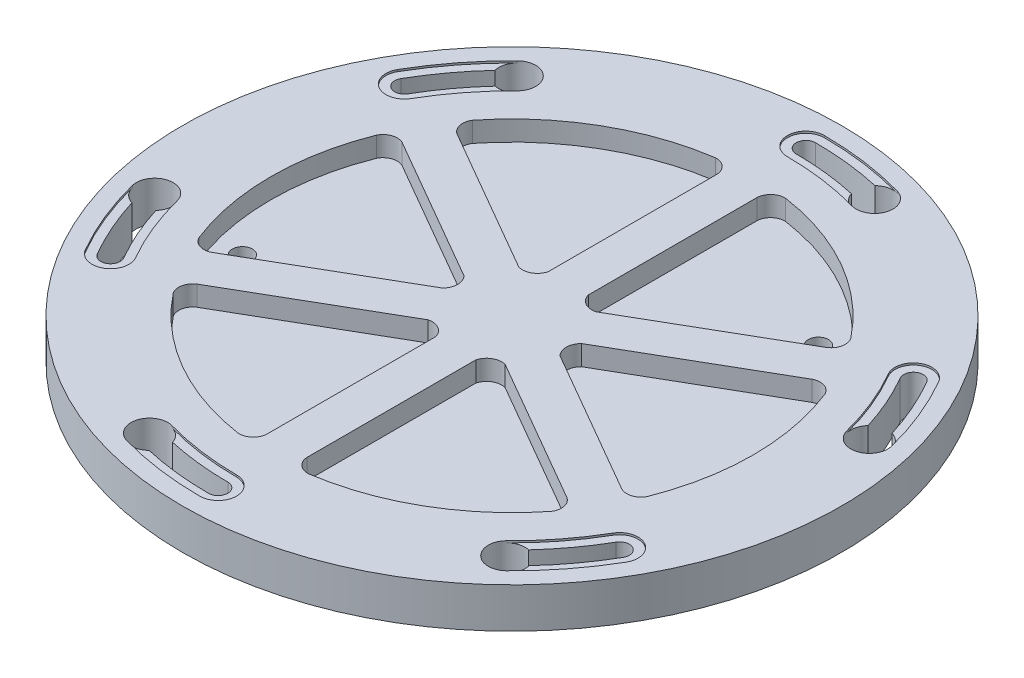
SolidWorks part; units mm, degrees
material "1060 Alloy"
ref_plane "Front Plane" through (0, 0, 0) normal (0, 0, 1) x (1, 0, 0)
ref_plane "Top Plane" through (0, 0, 0) normal (0, 1, 0) x (1, 0, 0)
ref_plane "Right Plane" through (0, 0, 0) normal (1, 0, 0) x (0, 0, -1)
sketch "Sketch1" plane through (0, 0, 0) normal (0, 1, 0) x (1, 0, 0)
  circle A0 centre (0, 0) radius 82
  arc A1 (0, 77.7102) -> (0, 68.5398) centre (0, 73.125) ccw
  arc A2 (0, 73.125) -> (19.8133, 70.3896) centre (0, 0) cw construction
  arc A3 (20.4672, 72.7124) -> (0, 75.5381) centre (0, 0) ccw construction
  arc A4 (19.1595, 68.0668) -> (0, 70.7119) centre (0, 0) ccw construction
  arc A5 (19.1595, 68.0668) -> (20.4672, 72.7124) centre (19.8133, 70.3896) ccw construction
  arc A6 (0, 75.5381) -> (0, 70.7119) centre (0, 73.125) ccw construction
  arc A7 (0, 73.125) -> (19.8133, 70.3896) centre (0, 0) cw construction
  arc A8 (21.0557, 74.8033) -> (0, 77.7102) centre (0, 0) ccw construction
  arc A9 (18.571, 65.9759) -> (0, 68.5398) centre (0, 0) ccw construction
  arc A10 (18.571, 65.9759) -> (21.0557, 74.8033) centre (19.8133, 70.3896) ccw construction
  arc A11 (0, 77.7102) -> (0, 68.5398) centre (0, 73.125) ccw construction
  arc A12 (15.4421, 69.0052) -> (16.6259, 73.6857) centre (19.8133, 70.3896) ccw
  arc A13 (0, 75.5381) -> (0, 70.7119) centre (0, 73.125) ccw
  arc A14 (0, 70.7119) -> (15.4421, 69.0052) centre (0, 0) cw
  arc A15 (0, 75.5381) -> (16.6259, 73.6857) centre (0, 0) cw
  arc A16 (0, 77.7102) -> (21.0557, 74.8033) centre (0, 0) cw
  arc A17 (0, 68.5398) -> (18.571, 65.9759) centre (0, 0) cw
  circle A18 centre (0, 0) radius 82
  arc A19 (67.299, 38.8551) -> (59.3572, 34.2699) centre (63.3281, 36.5625) ccw
  arc A20 (65.4179, 37.769) -> (61.2383, 35.356) centre (63.3281, 36.5625) ccw
  arc A21 (65.4179, 37.769) -> (72.1266, 22.4444) centre (0, 0) cw
  arc A22 (67.299, 38.8551) -> (75.3094, 19.1669) centre (0, 0) cw
  arc A23 (67.4813, 21.1293) -> (72.1266, 22.4444) centre (70.8659, 18.036) ccw
  arc A24 (61.2383, 35.356) -> (67.4813, 21.1293) centre (0, 0) cw
  arc A25 (59.3572, 34.2699) -> (66.4223, 16.905) centre (0, 0) cw
  circle A26 centre (0, 0) radius 82
  arc A27 (67.299, -38.8551) -> (59.3572, -34.2699) centre (63.3281, -36.5625) ccw
  arc A28 (65.4179, -37.769) -> (61.2383, -35.356) centre (63.3281, -36.5625) ccw
  arc A29 (65.4179, -37.769) -> (55.5007, -51.2413) centre (0, 0) cw
  arc A30 (67.299, -38.8551) -> (54.2537, -55.6364) centre (0, 0) cw
  arc A31 (52.0392, -47.8759) -> (55.5007, -51.2413) centre (51.0525, -52.3537) ccw
  arc A32 (61.2383, -35.356) -> (52.0392, -47.8759) centre (0, 0) cw
  arc A33 (59.3572, -34.2699) -> (47.8513, -49.0709) centre (0, 0) cw
  circle A34 centre (0, 0) radius 82
  arc A35 (0, -77.7102) -> (0, -68.5398) centre (0, -73.125) ccw
  arc A36 (0, -75.5381) -> (0, -70.7119) centre (0, -73.125) ccw
  arc A37 (0, -75.5381) -> (-16.6259, -73.6857) centre (0, 0) cw
  arc A38 (0, -77.7102) -> (-21.0557, -74.8033) centre (0, 0) cw
  arc A39 (-15.4421, -69.0052) -> (-16.6259, -73.6857) centre (-19.8133, -70.3896) ccw
  arc A40 (0, -70.7119) -> (-15.4421, -69.0052) centre (0, 0) cw
  arc A41 (0, -68.5398) -> (-18.571, -65.9759) centre (0, 0) cw
  circle A42 centre (0, 0) radius 82
  arc A43 (-67.299, -38.8551) -> (-59.3572, -34.2699) centre (-63.3281, -36.5625) ccw
  arc A44 (-65.4179, -37.769) -> (-61.2383, -35.356) centre (-63.3281, -36.5625) ccw
  arc A45 (-65.4179, -37.769) -> (-72.1266, -22.4444) centre (0, 0) cw
  arc A46 (-67.299, -38.8551) -> (-75.3094, -19.1669) centre (0, 0) cw
  arc A47 (-67.4813, -21.1293) -> (-72.1266, -22.4444) centre (-70.8659, -18.036) ccw
  arc A48 (-61.2383, -35.356) -> (-67.4813, -21.1293) centre (0, 0) cw
  arc A49 (-59.3572, -34.2699) -> (-66.4223, -16.905) centre (0, 0) cw
  circle A50 centre (0, 0) radius 82
  arc A51 (-67.299, 38.8551) -> (-59.3572, 34.2699) centre (-63.3281, 36.5625) ccw
  arc A52 (-65.4179, 37.769) -> (-61.2383, 35.356) centre (-63.3281, 36.5625) ccw
  arc A53 (-65.4179, 37.769) -> (-55.5007, 51.2413) centre (0, 0) cw
  arc A54 (-67.299, 38.8551) -> (-54.2537, 55.6364) centre (0, 0) cw
  arc A55 (-52.0392, 47.8759) -> (-55.5007, 51.2413) centre (-51.0525, 52.3537) ccw
  arc A56 (-61.2383, 35.356) -> (-52.0392, 47.8759) centre (0, 0) cw
  arc A57 (-59.3572, 34.2699) -> (-47.8513, 49.0709) centre (0, 0) cw
  point P7 (10.0006, 72.4379)
  point P15 (10.0006, 72.4379)
  point P111 (0, 0)
  dimension "D1" = 6
extrude "Boss-Extrude1" add sketch "Sketch1" along normal blind 10 contours A0 A57 A51 A54 A55 A49 A43 A46 A47 A41 A35 A38 A39 A33 A27 A30 A31 A25 A19 A22 A23 A17 A1 A16 A12 region at (0, 0, 0)
extrude "Boss-Extrude3" add sketch "Sketch1<4>" along normal blind 9.525 contours A43 A49 A47 A48 A44 A45 A46 region at (-71.7086, 0, 29.1755)
sketch "Sketch1<4>" plane through (0, 0, 0) normal (0, 1, 0) x (1, 0, 0) same geometry as "Sketch1"
pattern_circular "CirPattern1" count 6 over 360 about axis through (0, 10, 0) along (0, 1, 0) of "Boss-Extrude3"
sketch "Sketch2" plane through (0, 10, 0) normal (0, 1, 0) x (1, 0, 0)
  line L0 (-28.4808, 10.6699) -> (-51.0159, 23.6805)
  line L1 (-28.4808, 10.6699) -> (-14.6202, 2.6675)
  line L2 (-14.6202, -2.6675) -> (-28.4808, -10.6699)
  line L3 (-28.4808, -10.6699) -> (-51.0159, -23.6805)
  line L4 (-5, 30) -> (-5, 56.0213)
  line L5 (-5, 30) -> (-5, 13.9952)
  line L6 (-9.6202, 11.3277) -> (-23.4808, 19.3301)
  line L7 (-23.4808, 19.3301) -> (-46.0159, 32.3408)
  line L8 (-23.4808, -19.3301) -> (-9.6202, -11.3277)
  line L9 (-5, -13.9952) -> (-5, -30)
  line L10 (-23.4808, -19.3301) -> (-46.0159, -32.3408)
  line L11 (-5, -30) -> (-5, -56.0213)
  line L12 (23.4808, 19.3301) -> (46.0159, 32.3408)
  line L13 (23.4808, 19.3301) -> (9.6202, 11.3277)
  line L14 (5, 13.9952) -> (5, 30)
  line L15 (5, 30) -> (5, 56.0213)
  line L16 (28.4808, -10.6699) -> (51.0159, -23.6805)
  line L17 (28.4808, -10.6699) -> (14.6202, -2.6675)
  line L18 (14.6202, 2.6675) -> (28.4808, 10.6699)
  line L19 (28.4808, 10.6699) -> (51.0159, 23.6805)
  line L20 (5, -30) -> (5, -56.0213)
  line L21 (5, -30) -> (5, -13.9952)
  line L22 (9.6202, -11.3277) -> (23.4808, -19.3301)
  line L23 (23.4808, -19.3301) -> (46.0159, -32.3408)
  arc A0 (-47.034, -37.2532) -> (-8.7452, -59.3593) centre (0, 0) ccw
  arc A1 (-9.6202, -11.3277) -> (-5, -13.9952) centre (-8.6438, -14.9716) cw
  arc A2 (-47.034, -37.2532) -> (-8.7452, -59.3593) centre (0, 0) ccw
  arc A3 (-47.034, -37.2532) -> (-46.0159, -32.3408) centre (-44.0688, -35.3061) cw
  arc A4 (-5, -56.0213) -> (-8.7452, -59.3593) centre (-8.5416, -55.8177) cw
  arc A5 (-55.7792, 22.1061) -> (-51.0159, 23.6805) centre (-52.6103, 20.5116) cw
  arc A6 (-14.6202, 2.6675) -> (-14.6202, -2.6675) centre (-17.2877, 0) cw
  arc A7 (-51.0159, -23.6805) -> (-55.7792, -22.1061) centre (-52.6103, -20.5116) cw
  arc A8 (-47.034, -37.2532) -> (-8.7452, -59.3593) centre (0, 0) ccw
  arc A9 (-8.7452, 59.3593) -> (-5, 56.0213) centre (-8.5416, 55.8177) cw
  arc A10 (-5, 13.9952) -> (-9.6202, 11.3277) centre (-8.6438, 14.9716) cw
  arc A11 (-46.0159, 32.3408) -> (-47.034, 37.2532) centre (-44.0688, 35.3061) cw
  arc A12 (-47.034, -37.2532) -> (-8.7452, -59.3593) centre (0, 0) ccw
  arc A13 (47.034, 37.2532) -> (46.0159, 32.3408) centre (44.0688, 35.3061) cw
  arc A14 (9.6202, 11.3277) -> (5, 13.9952) centre (8.6438, 14.9716) cw
  arc A15 (5, 56.0213) -> (8.7452, 59.3593) centre (8.5416, 55.8177) cw
  arc A16 (-47.034, -37.2532) -> (-8.7452, -59.3593) centre (0, 0) ccw
  arc A17 (55.7792, -22.1061) -> (51.0159, -23.6805) centre (52.6103, -20.5116) cw
  arc A18 (14.6202, -2.6675) -> (14.6202, 2.6675) centre (17.2877, 0) cw
  arc A19 (51.0159, 23.6805) -> (55.7792, 22.1061) centre (52.6103, 20.5116) cw
  arc A20 (-47.034, -37.2532) -> (-8.7452, -59.3593) centre (0, 0) ccw
  arc A21 (8.7452, -59.3593) -> (5, -56.0213) centre (8.5416, -55.8177) cw
  arc A22 (5, -13.9952) -> (9.6202, -11.3277) centre (8.6438, -14.9716) cw
  arc A23 (46.0159, -32.3408) -> (47.034, -37.2532) centre (44.0688, -35.3061) cw
  arc A24 (8.7452, -59.3593) -> (47.034, -37.2532) centre (0, 0) ccw
  arc A25 (8.7452, -59.3593) -> (47.034, -37.2532) centre (0, 0) ccw
  arc A26 (8.7452, -59.3593) -> (47.034, -37.2532) centre (0, 0) ccw
  arc A27 (8.7452, -59.3593) -> (47.034, -37.2532) centre (0, 0) ccw
  arc A28 (8.7452, -59.3593) -> (47.034, -37.2532) centre (0, 0) ccw
  arc A29 (8.7452, -59.3593) -> (47.034, -37.2532) centre (0, 0) ccw
  arc A30 (-55.7792, 22.1061) -> (-55.7792, -22.1061) centre (0, 0) ccw
  arc A31 (-55.7792, 22.1061) -> (-55.7792, -22.1061) centre (0, 0) ccw
  arc A32 (-55.7792, 22.1061) -> (-55.7792, -22.1061) centre (0, 0) ccw
  arc A33 (-55.7792, 22.1061) -> (-55.7792, -22.1061) centre (0, 0) ccw
  arc A34 (-55.7792, 22.1061) -> (-55.7792, -22.1061) centre (0, 0) ccw
  arc A35 (-55.7792, 22.1061) -> (-55.7792, -22.1061) centre (0, 0) ccw
  arc A36 (-8.7452, 59.3593) -> (-47.034, 37.2532) centre (0, 0) ccw
  arc A37 (-8.7452, 59.3593) -> (-47.034, 37.2532) centre (0, 0) ccw
  arc A38 (-8.7452, 59.3593) -> (-47.034, 37.2532) centre (0, 0) ccw
  arc A39 (-8.7452, 59.3593) -> (-47.034, 37.2532) centre (0, 0) ccw
  arc A40 (-8.7452, 59.3593) -> (-47.034, 37.2532) centre (0, 0) ccw
  arc A41 (-8.7452, 59.3593) -> (-47.034, 37.2532) centre (0, 0) ccw
  arc A42 (47.034, 37.2532) -> (8.7452, 59.3593) centre (0, 0) ccw
  arc A43 (47.034, 37.2532) -> (8.7452, 59.3593) centre (0, 0) ccw
  arc A44 (47.034, 37.2532) -> (8.7452, 59.3593) centre (0, 0) ccw
  arc A45 (47.034, 37.2532) -> (8.7452, 59.3593) centre (0, 0) ccw
  arc A46 (47.034, 37.2532) -> (8.7452, 59.3593) centre (0, 0) ccw
  arc A47 (47.034, 37.2532) -> (8.7452, 59.3593) centre (0, 0) ccw
  arc A48 (55.7792, -22.1061) -> (55.7792, 22.1061) centre (0, 0) ccw
  arc A49 (55.7792, -22.1061) -> (55.7792, 22.1061) centre (0, 0) ccw
  arc A50 (55.7792, -22.1061) -> (55.7792, 22.1061) centre (0, 0) ccw
  arc A51 (55.7792, -22.1061) -> (55.7792, 22.1061) centre (0, 0) ccw
  arc A52 (55.7792, -22.1061) -> (55.7792, 22.1061) centre (0, 0) ccw
  arc A53 (55.7792, -22.1061) -> (55.7792, 22.1061) centre (0, 0) ccw
  point P83 (0, 0)
  dimension "D1" = 6
extrude "Cut-Extrude1" cut sketch "Sketch2" against normal blind 5 contours A5 A30 A7 L3 L2 A6 L1 L0 | A9 A36 A11 L7 L6 A10 L5 L4 | A13 A42 A15 L15 L14 A14 L13 L12 | A17 A48 A19 L19 L18 A18 L17 L16 | A21 A24 A23 L23 L22 A22 L21 L20 | A4 L11 L9 A1 L8 L10 A3 A0 region at (-42.1694, 10, 0) region at (-21.0847, 10, -36.5198) region at (-21.0847, 10, 36.5198) region at (21.0847, 10, -36.5198) region at (42.1694, 10, 0) region at (21.0847, 10, 36.5198)
sketch "Sketch3" plane through (0, 0, 0) normal (0, -1, 0) x (1, 0, 0)
  circle A0 centre (0, 0) radius 67.5
  circle A1 centre (-51.6852, 15.404) radius 2.5
  circle A2 centre (39.4674, -36.7555) radius 2.5
  point P6 (0, 0)
  point P7 (0, 0)
extrude "Cut-Extrude2" cut sketch "Sketch3" against normal blind 5 contours A1
extrude "Cut-Extrude3" cut sketch "Sketch3<3>" against normal blind 5 contours A2
sketch "Sketch3<3>" plane through (0, 0, 0) normal (0, -1, 0) x (1, 0, 0) same geometry as "Sketch3"
